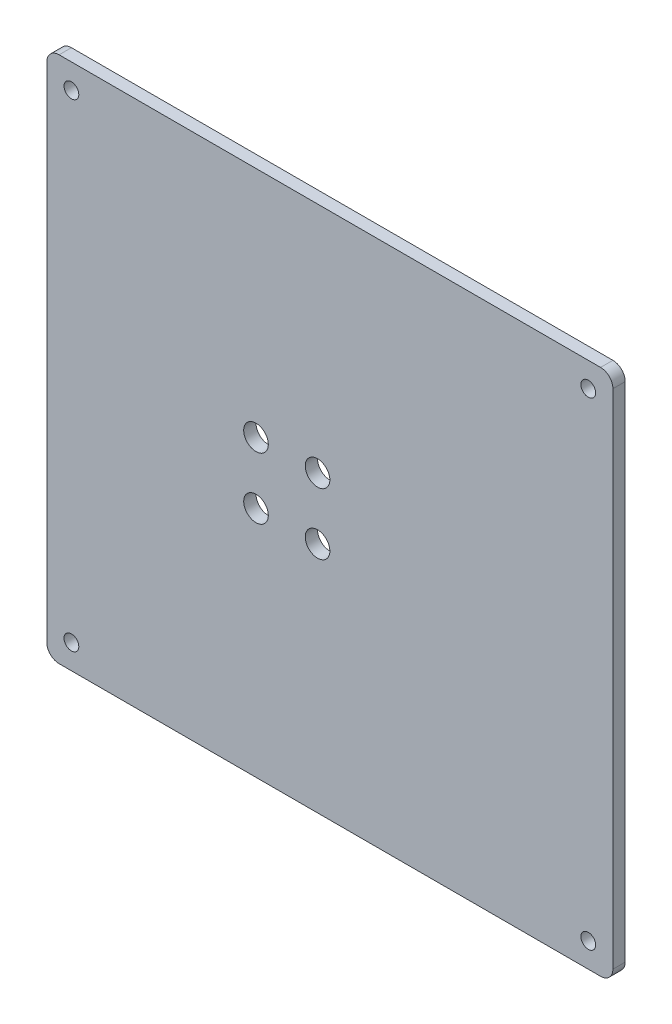
SolidWorks part; units mm, degrees
ref_plane "前视基准面" through (0, 0, 0) normal (0, 0, 1) x (1, 0, 0)
ref_plane "上视基准面" through (0, 0, 0) normal (0, 1, 0) x (1, 0, 0)
ref_plane "右视基准面" through (0, 0, 0) normal (1, 0, 0) x (0, 0, -1)
sketch "草图1" plane through (0, 0, 0) normal (0, 0, 1) x (1, 0, 0)
  line L1 (95, -87.125) -> (-95, -87.125)
  line L2 (95, -87.125) -> (95, 87.125)
  line L3 (95, 87.125) -> (-95, 87.125)
  line L4 (-95, -87.125) -> (-95, 87.125)
  line L5 (95, -87.125) -> (-95, 87.125) construction
  line L6 (95, 87.125) -> (-95, -87.125) construction
  line L7 (90, -82.125) -> (-90, -82.125)
  line L8 (90, -82.125) -> (90, 82.125)
  line L9 (90, 82.125) -> (-90, 82.125)
  line L10 (-90, -82.125) -> (-90, 82.125)
  line L11 (90, -82.125) -> (-90, 82.125) construction
  line L12 (90, 82.125) -> (-90, -82.125) construction
  point P0 (0, 0)
  point P6 (0, 0)
  dimension "D1" = 190
  dimension "D2" = 174.25
  dimension "D3" = 5
  dimension "D4" = 5
extrude "凸台-拉伸1" add sketch "草图1" along normal blind 8
fillet "圆角1" radius 5 8 edges at (-90, 82.125, 4) (90, 82.125, 4) (90, -82.125, 4) (-90, -82.125, 4) (95, -87.125, 4) (-95, -87.125, 4) (-95, 87.125, 4) (95, 87.125, 4)
sketch "草图2" plane through (0, 0, 8) normal (0, 0, 1) x (1, 0, 0)
  line L1 (115, -107.125) -> (-115, -107.125)
  line L2 (115, -107.125) -> (115, 107.125)
  line L3 (115, 107.125) -> (-115, 107.125)
  line L4 (-115, -107.125) -> (-115, 107.125)
  line L5 (115, -107.125) -> (-115, 107.125) construction
  line L6 (115, 107.125) -> (-115, -107.125) construction
  point P0 (0, 0)
  dimension "D1" = 214.25
  dimension "D2" = 230
extrude "凸台-拉伸2" add sketch "草图2" along normal blind 5
fillet "圆角2" radius 5 4 edges at (-115, 107.125, 10.5) (115, 107.125, 10.5) (115, -107.125, 10.5) (-115, -107.125, 10.5)
sketch "草图3" plane through (0, 0, 13) normal (0, 0, 1) x (1, 0, 0)
  line L0 (110, 107.125) -> (-110, 107.125) construction
  line L1 (-115, 102.125) -> (-115, -102.125) construction
  line L2 (-110, -107.125) -> (110, -107.125) construction
  line L3 (115, -102.125) -> (115, 102.125) construction
  point P0 (-105, 97.125)
  point P1 (-105, -97.125)
  point P2 (105, -97.125)
  point P3 (105, 97.125)
  dimension "D1" = 10
  dimension "D2" = 10
  dimension "D3" = 10
  dimension "D4" = 10
  dimension "D5" = 10
  dimension "D6" = 10
  dimension "D7" = 10
  dimension "D8" = 10
hole_wizard "Ø6.0 (6) 直径孔1" positions "草图4" profile "草图5" hole size "Ø6.0" standard "GB" end condition up to next
sketch "草图4" plane through (0, 0, 13) normal (0, 0, 1) x (1, 0, 0)
  point P0 (-105, 97.125)
  point P3 (105, 97.125)
  point P6 (105, -97.125)
  point P9 (-105, -97.125)
sketch "草图5" plane through (-105, 97.125, 13) normal (1, 0, 0) x (0, -1, 0)
  line L0 (0, 0) -> (0, 5)
  line L1 (0, 5) -> (3, 5)
  line L2 (3, 5) -> (3, 0)
  line L5 (3, 0) -> (0, 0)
  line L11 (0, -6.35) -> (0, 107.95) construction
  dimension "通孔孔直径" = 6
  dimension "通孔孔深度" = 5
sketch "草图7" plane through (0, 0, 13) normal (0, 0, 1) x (1, 0, 0)
  line L0 (115, -102.125) -> (115, 102.125) construction
  point P0 (-5, 12.5)
  point P1 (-30, 12.5)
  point P2 (-30, -12.5)
  point P3 (-5, -12.5)
  dimension "D1" = 25
  dimension "D2" = 25
  dimension "D3" = 25
  dimension "D4" = 25
  dimension "D5" = 120
  dimension "D6" = 12.5
hole_wizard "Ø10.0 (10) 直径孔1" positions "草图8" profile "草图9" hole size "Ø10.0" standard "GB" end condition through all
sketch "草图8" plane through (0, 0, 13) normal (0, 0, 1) x (1, 0, 0)
  point P0 (-30, 12.5)
  point P3 (-5, 12.5)
  point P6 (-5, -12.5)
  point P9 (-30, -12.5)
sketch "草图9" plane through (-30, 12.5, 13) normal (1, 0, 0) x (0, -1, 0)
  line L0 (0, 0) -> (0, 13)
  line L1 (0, 13) -> (5, 13)
  line L2 (5, 13) -> (5, 0)
  line L5 (5, 0) -> (0, 0)
  line L11 (0, -6.35) -> (0, 107.95) construction
  dimension "通孔孔直径" = 10
  dimension "通孔孔深度" = 13
